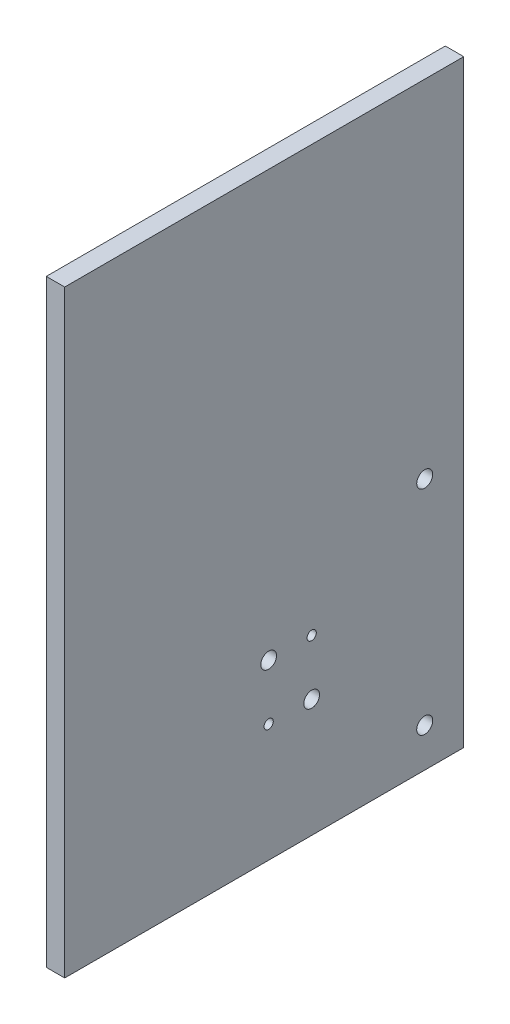
SolidWorks part; units mm, degrees
ref_plane "Front Plane" through (0, 0, 0) normal (1, 0, 0) x (0, 1, 0)
ref_plane "Top Plane" through (0, 0, 0) normal (0, 0, 1) x (0, 1, 0)
ref_plane "Right Plane" through (0, 0, 0) normal (0, 1, 0) x (-1, 0, 0)
sketch "Sketch1" plane through (0, 0, 0) normal (1, 0, 0) x (0, 1, 0)
  line L0 (0, 25) -> (0, -25) construction
  line L1 (-47.4, -25) -> (47.4, -25) construction
  line L2 (-47.4, -25) -> (-47.4, 25) construction
  line L3 (-47.4, 25) -> (47.4, 25) construction
  line L4 (47.4, -25) -> (47.4, 25) construction
  line L5 (-47.4, -25) -> (47.4, 25) construction
  line L6 (-47.4, 25) -> (47.4, -25) construction
  line L7 (-47.4, 16) -> (47.4, 16) construction
  line L8 (-9, -7) -> (9, -7) construction
  line L9 (-9, -7) -> (-9, 7) construction
  line L10 (-9, 7) -> (9, 7) construction
  line L11 (9, -7) -> (9, 7) construction
  line L12 (-9, -7) -> (9, 7) construction
  line L13 (-9, 7) -> (9, -7) construction
  line L14 (-34.7, -15) -> (34.7, -15) construction
  line L15 (-34.7, -15) -> (-34.7, 15) construction
  line L16 (-34.7, 15) -> (34.7, 15) construction
  line L17 (34.7, -15) -> (34.7, 15) construction
  line L18 (-34.7, -15) -> (34.7, 15) construction
  line L19 (-34.7, 15) -> (34.7, -15) construction
  line L20 (-47.4, -25) -> (47.4, -25) construction
  line L21 (-47.4, -25) -> (-47.4, -56.5)
  line L22 (-47.4, -56.5) -> (47.4, -56.5)
  line L23 (47.4, -25) -> (47.4, -56.5) construction
  line L24 (-47.4, -56.5) -> (-34.7, -56.5) construction
  line L25 (-47.4, -56.5) -> (-47.4, -43.8) construction
  line L26 (-47.4, -43.8) -> (-34.7, -43.8) construction
  line L27 (-34.7, -56.5) -> (-34.7, -43.8) construction
  line L28 (47.4, -56.5) -> (34.7, -56.5) construction
  line L29 (47.4, -56.5) -> (47.4, -43.8) construction
  line L30 (47.4, -43.8) -> (34.7, -43.8) construction
  line L31 (34.7, -56.5) -> (34.7, -43.8) construction
  line L32 (47.4, -25) -> (47.4, 16) construction
  line L33 (-47.4, 16) -> (-47.4, -25)
  line L35 (47.4, 16) -> (147.4, 16) construction
  line L36 (47.4, 16) -> (47.4, -56.5) construction
  line L37 (47.4, -56.5) -> (147.4, -56.5)
  line L38 (147.4, 16) -> (147.4, -56.5)
  line L39 (-47.4, 16) -> (147.4, 16) construction
  line L40 (-47.4, 16) -> (-47.4, 73.4)
  line L41 (-47.4, 73.4) -> (147.4, 73.4)
  line L42 (147.4, 16) -> (147.4, 73.4)
  circle A0 centre (-9, 7) radius 1.5
  circle A1 centre (-9, -7) radius 2.555
  circle A2 centre (9, -7) radius 1.5
  circle A3 centre (9, 7) radius 2.555
  circle A4 centre (-34.7, 15) radius 2.555 construction
  circle A5 centre (-34.7, -15) radius 2.555 construction
  circle A6 centre (34.7, 15) radius 2.555 construction
  circle A7 centre (34.7, -15) radius 2.555 construction
  circle A8 centre (-34.7, -43.8) radius 2.6
  circle A9 centre (34.7, -43.8) radius 2.6
  point P0 (0, 0)
  point P8 (0, 0)
  point P17 (0, 0)
  point P43 (148.0257, 16)
  dimension "D5" = 5.11
  dimension "D6" = 3
  dimension "D9" = 5.11
  dimension "D10" = 5.11
  dimension "D11" = 5.11
  dimension "D12" = 3
  dimension "D13" = 3
  dimension "D17" = 5.2
  dimension "D18" = 9
  dimension "D1" = 14
  dimension "D2" = 18
  dimension "D3" = 94.8
  dimension "D4" = 50
  dimension "D7" = 12.7
  dimension "D8" = 30
  dimension "D14" = 31.5
  dimension "D15" = 12.7
  dimension "D16" = 12.7
  dimension "D19" = 100
  dimension "D20" = 57.4
extrude "Boss-Extrude1" add sketch "Sketch1" along normal blind 6
